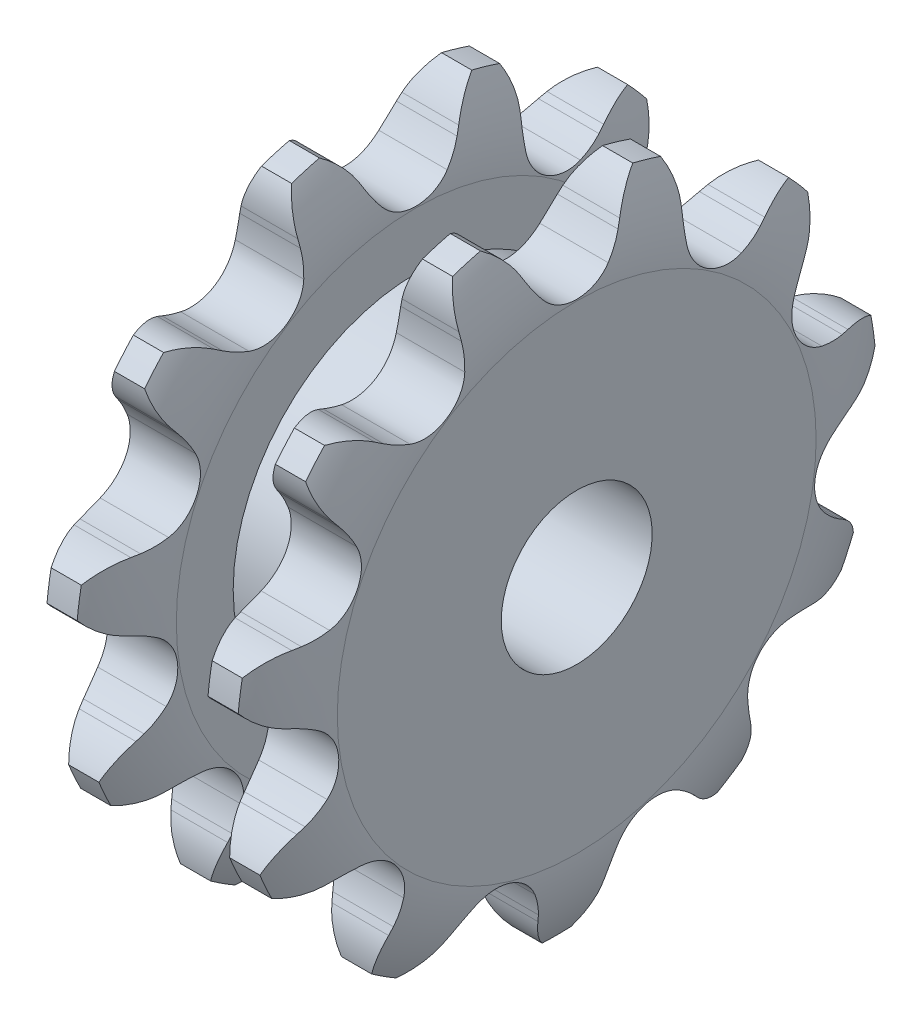
SolidWorks part; units mm, degrees
ref_plane "Plane1" through (0, 0, 0) normal (0, 0, 1) x (1, 0, 0)
ref_plane "Plane2" through (0, 0, 0) normal (0, 1, 0) x (1, 0, 0)
ref_plane "Plane3" through (0, 0, 0) normal (1, 0, 0) x (0, 0, -1)
sketch "Clipboard" plane through (0, 0, 0) normal (0, 1, 0) x (1, 0, 0)
  line L0 (0, 0) -> (6.2333, -1.2116)
  line L1 (-15, 0) -> (100, 0) construction
  line L2 (0, 0) -> (-0.5301, 0.5991)
  line L3 (0, 0) -> (-2.9891, 1.1425)
  line L4 (0, 0) -> (3.043, 0.5915)
  line L5 (0, 0) -> (-89.0105, -33.1983)
  line L6 (0, 0) -> (-7.6265, -5.1456)
  line L7 (-0.5301, 0.5991) -> (92.0355, 21.9696)
  line L8 (-76.2, 38.1) -> (-75.2, 38.1)
  line L9 (-73.2358, 39.4872) -> (-73.0836, 39.4947)
  line L10 (-73.0533, 76.1892) -> (-66.6533, 76.1892)
  circle A0 centre (0, 0) radius 1.651
  circle A1 centre (0, 0) radius 4
  circle A2 centre (0, 0) radius 4
  dimension "Num_teeth" = 11
  dimension "Thickness" = 9.2
sketch "BasProSke" plane through (0, 0, 0) normal (0, 1, 0) x (1, 0, 0)
  line L0 (-10, 0) -> (60, 0) construction
  line L1 (0, 0) -> (0, 9.5181)
  line L2 (0, 0) -> (9.2, 0)
  line L3 (9.2, 0) -> (9.2, 9.5181)
  line L4 (8.4, 12.7181) -> (0.8, 12.7181)
  arc A0 (0, 9.5181) -> (0.8, 12.7181) centre (6.8, 9.5181) cw
  arc A1 (9.2, 9.5181) -> (8.4, 12.7181) centre (2.4, 9.5181) ccw
  dimension "D1" = 6.8
  dimension "Thickness" = 9.2
  dimension "Diameter" = 25.4361
  dimension "H1" = 3.2
  dimension "G1" = 0.8
revolve "Base-Revolve" add sketch "BasProSke" angle 360 about L0
sketch "GrvSke" plane through (0, 0, 0) normal (0, 1, 0) x (1, 0, 0)
  line L0 (2.8, 9.5181) -> (2.8, 7.2571)
  line L1 (2.8, 7.2571) -> (6.4, 7.2571)
  line L2 (6.4, 7.2571) -> (6.4, 9.5181)
  line L3 (2, 12.7181) -> (7.2, 12.7181)
  line L4 (4.6, 0) -> (4.6, 52.07) construction
  line L5 (-10, 0) -> (60, 0) construction
  line L6 (0, 0) -> (35.56, 0) construction
  arc A0 (6.4, 9.5181) -> (7.2, 12.7181) centre (13.2, 9.5181) cw
  arc A1 (2.8, 9.5181) -> (2, 12.7181) centre (-4, 9.5181) ccw
  dimension "Diameter" = 25.4361
  dimension "H1" = 3.2
  dimension "G1" = 0.8
revolve "Groove" cut sketch "GrvSke" angle 360 about L6
pattern_linear "Grooves" [suppressed]
sketch "TooCutSke" plane through (0, 0, 0) normal (1, 0, 0) x (0, 0, -1)
  line L0 (1.8371, 10.977) -> (1.9787, 11.2486)
  line L1 (0, 0) -> (0, 107) construction
  line L2 (0, 11.2696) -> (-10, 11.2696) construction
  line L3 (-1.8371, 10.977) -> (-1.9787, 11.2486)
  arc A0 (1.2916, 10.1682) -> (1.8371, 10.977) centre (-2.01, 12.9835) ccw
  arc A1 (1.2916, 10.1682) -> (-1.2916, 10.1682) centre (0, 11.2696) cw
  arc A2 (1.9787, 11.2486) -> (4.4355, 12.7381) centre (4.4355, 9.9672) cw
  arc A3 (-1.2916, 10.1682) -> (-1.8371, 10.977) centre (2.01, 12.9835) cw
  arc A4 (-1.9787, 11.2486) -> (-4.4355, 12.7381) centre (-4.4355, 9.9672) ccw
  arc A5 (4.4355, 12.7381) -> (-4.4355, 12.7381) centre (0, 0) ccw
  dimension "Pitch_radius" = 11.2696
  dimension "V" = 1.3024
extrude "ToothCut" cut sketch "TooCutSke" along normal through all
pattern_circular "TeethCuts" count 11 every 32.727 about axis through (-10, 0, 0) along (1, 0, 0) of "ToothCut"
sketch "HubNeaOneSke" plane through (0, 0, 0) normal (-1, 0, 0) x (0, 0, 1)
  circle A0 centre (0, 0) radius 4
  dimension "Diameter" = 8
extrude "HubNearOne" [suppressed] add sketch "HubNeaOneSke" along normal blind 85.8005
sketch "HubNeaBotSke" plane through (0, 0, 0) normal (-1, 0, 0) x (0, 0, 1)
  circle A0 centre (0, 0) radius 4
  dimension "Diameter" = 8
extrude "HubNearBoth" [suppressed] add sketch "HubNeaBotSke" along normal blind 42.9002
ref_plane "FarPln" through (9.2, 0, 0) normal (1, 0, 0) x (0, 0, -1)
sketch "HubFarSke" plane through (9.2, 0, 0) normal (1, 0, 0) x (0, 0, -1)
  circle A0 centre (0, 0) radius 4
  dimension "Diameter" = 8
extrude "HubFar" [suppressed] add sketch "HubFarSke" along normal blind 42.9002
sketch "BorSke" plane through (0, 0, 0) normal (1, 0, 0) x (0, 0, -1)
  circle A0 centre (0, 0) radius 3
  dimension "Diameter" = 6
extrude "Bore" cut sketch "BorSke" along normal mid plane 190.001
sketch "KeySke" plane through (0, 0, 0) normal (1, 0, 0) x (0, 0, -1)
  line L0 (-1, 0) -> (-1, 4)
  line L1 (-1, 4) -> (1, 4)
  line L2 (1, 4) -> (1, 0)
  line L3 (0, 0) -> (0, 34) construction
  line L4 (-1, 0) -> (1, 0)
  dimension "Offset" = 4
  dimension "Width" = 2
extrude "Keyway" [suppressed] cut sketch "KeySke" along normal mid plane 190.001
pattern_circular "Keyway2" [suppressed] count 2 every 90 about axis through (-10, 0, 0) along (1, 0, 0) reverse direction yes
equation "' \"Pitch@Clipboard\" = 6.35"
equation "' \"Num_strands@Clipboard\" = 2"
equation "' \"Num_teeth@Clipboard\" = 11"
equation "' \"Hub_dia@Clipboard\" = 8"
equation "' \"Overall_len@Clipboard\" = 95"
equation "' \"Diameter@BorSke\" = 6"
equation "' \"T_dim@Clipboard\" = 1"
equation "' \"Width@KeySke\" = 2"
equation "' \"Dr@Clipboard\" = 3.302"
equation "' \"Face_width@Clipboard\" = 2.8"
equation "' \"Chamfer_dep@Clipboard\" = 3.2"
equation "' \"Chamfer_wid@Clipboard\" = 0.8"
equation "' \"Transv_pitch@Clipboard\" = 6.4"
equation "' \"Show_teeth@Clipboard\" = 11"
equation "\"Num_teeth@Clipboard\" = int( \"Num_teeth@Clipboard\" )"
equation "\"Num_teeth@Clipboard\" = ((sgn( \"Num_teeth@Clipboard\" - 5.0)+1)*( \"Num_teeth@Clipboard\" - 5.0))/2 +5.0"
equation "\"Num_teeth@Clipboard\" = ((sgn( \"Num_teeth@Clipboard\" - 200.0)-1)*( \"Num_teeth@Clipboard\" - 200.0))/-2 +200.0"
equation "\"MHD@Clipboard\" = \"Pitch@Clipboard\" * (1.0 / tan(3.14159265 / \"Num_teeth@Clipboard\" ) - 1.0) - 0.762"
equation "\"Thickness@Clipboard\"  = \"Face_width@Clipboard\" + (\"Num_strands@Clipboard\" - 1) * \"Transv_pitch@Clipboard\""
equation "\"OAL@Clipboard\" = \"Thickness@Clipboard\""
equation "\"MHD@Clipboard\" = ((sgn( \"MHD@Clipboard\" - \"Hub_dia@Clipboard\" )-1)*( \"MHD@Clipboard\" - \"Hub_dia@Clipboard\" ))/-2+ \"Hub_dia@Clipboard\""
equation "\"OAL@Clipboard\" = ((sgn( \"OAL@Clipboard\" - \"Overall_len@Clipboard\" )+1)*( \"OAL@Clipboard\" - \"Overall_len@Clipboard\" ))/2 + \"Overall_len@Clipboard\" + 0.0005"
equation "\"Num_teeth@TeethCuts\" = int( \"Show_teeth@Clipboard\" ) + 1"
equation "\"Num_teeth@TeethCuts\" = ((sgn( \"Num_teeth@TeethCuts\" - \"Num_teeth@Clipboard\" )-1)*( \"Num_teeth@TeethCuts\" - \"Num_teeth@Clipboard\" ))/-2+ \"Num_teeth@Clipboard\""
equation "\"Num_teeth@TeethCuts\" = ((sgn( \"Num_teeth@TeethCuts\" - 2.0)+1)*( \"Num_teeth@TeethCuts\" - 2.0))/2 +2.0"
equation "\"Angle@TeethCuts\" = 360.0 / \"Num_teeth@Clipboard\""
equation "\"Pitch_radius@TooCutSke\" = ( \"Pitch@Clipboard\" / 2.0) / sin(3.14159265 / \"Num_teeth@Clipboard\" )  'ma"
equation "\"R@TooCutSke\"  = \"Dr@Clipboard\" * 0.5025 + 0.0381"
equation "\"A@TooCutSke\" = 35.0 + (60.0 / \"Num_teeth@Clipboard\")"
equation "\"E@TooCutSke\"  = \"Dr@Clipboard\" * 1.3025 + 0.0381"
equation "\"B@TooCutSke\"  = 18.0 - (56.0 / \"Num_teeth@Clipboard\" )"
equation "\"W@TooCutSke\" = 1.4 * \"Dr@Clipboard\" * cos(3.14159265 / \"Num_teeth@Clipboard\" )"
equation "\"V@TooCutSke\" = 1.4 * \"Dr@Clipboard\" * sin(3.14159265 / \"Num_teeth@Clipboard\" )"
equation "\"Diameter@BasProSke\" = 2.0 * ( (0.3 * \"Pitch@Clipboard\" ) +  \"Pitch@Clipboard\" / 2.0 / tan(3.14159265 / \"Num_teeth@Clipboard\" ))"
equation "\"Thickness@BasProSke\"  = \"Thickness@Clipboard\""
equation "\"G1@BasProSke\" =  \"Chamfer_wid@Clipboard\""
equation "\"G2@BasProSke\" =  \"Chamfer_wid@Clipboard\""
equation "\"H1@BasProSke\" =  \"Chamfer_dep@Clipboard\""
equation "\"H2@BasProSke\" =  \"Chamfer_dep@Clipboard\""
equation "\"Diameter@GrvSke\" = \"Diameter@BasProSke\""
equation "\"G1@GrvSke\" = \"Chamfer_wid@Clipboard\""
equation "\"H1@GrvSke\" = \"Chamfer_dep@Clipboard\""
equation "\"Grv_diam@GrvSke\" =  \"Pitch@Clipboard\" * (1.0 / tan(3.14159265 / \"Num_teeth@Clipboard\" ) - 1.0) - 0.762"
equation "\"Grv_width@GrvSke\" =  \"Transv_pitch@Clipboard\" - \"Face_width@Clipboard\""
equation "\"Offset@GrvSke\" = \"Grv_width@GrvSke\" / 2.0 + \"Face_width@Clipboard\""
equation "\"Offset@Grooves\" = \"Transv_pitch@Clipboard\""
equation "\"Num_grvs@Grooves\" = \"Num_strands@Clipboard\""
equation "\"Num_grvs@Grooves\" = \"Num_grvs@Grooves\" - 1 * sgn( \"Num_grvs@Grooves\" -1)"
equation "\"Diameter@HubNeaOneSke\" = \"MHD@Clipboard\""
equation "\"Length@HubNearOne\" = \"OAL@Clipboard\" - \"Thickness@BasProSke\""
equation "\"Diameter@HubNeaBotSke\" = \"MHD@Clipboard\""
equation "\"Length@HubNearBoth\" = ( \"OAL@Clipboard\" - \"Thickness@BasProSke\" ) / 2.0"
equation "\"Thickness@FarPln\" = \"Thickness@BasProSke\""
equation "\"Diameter@HubFarSke\" = \"MHD@Clipboard\""
equation "\"Length@HubFar\" = ( \"OAL@Clipboard\" - \"Thickness@BasProSke\" ) / 2.0"
equation "\"D1@Bore\" = \"OAL@Clipboard\" * 2.0"
equation "\"D1@Keyway\" = \"OAL@Clipboard\" * 2.0"
equation "\"Offset@KeySke\" = \"T_dim@Clipboard\" + \"Diameter@BorSke\" / 2.0"
